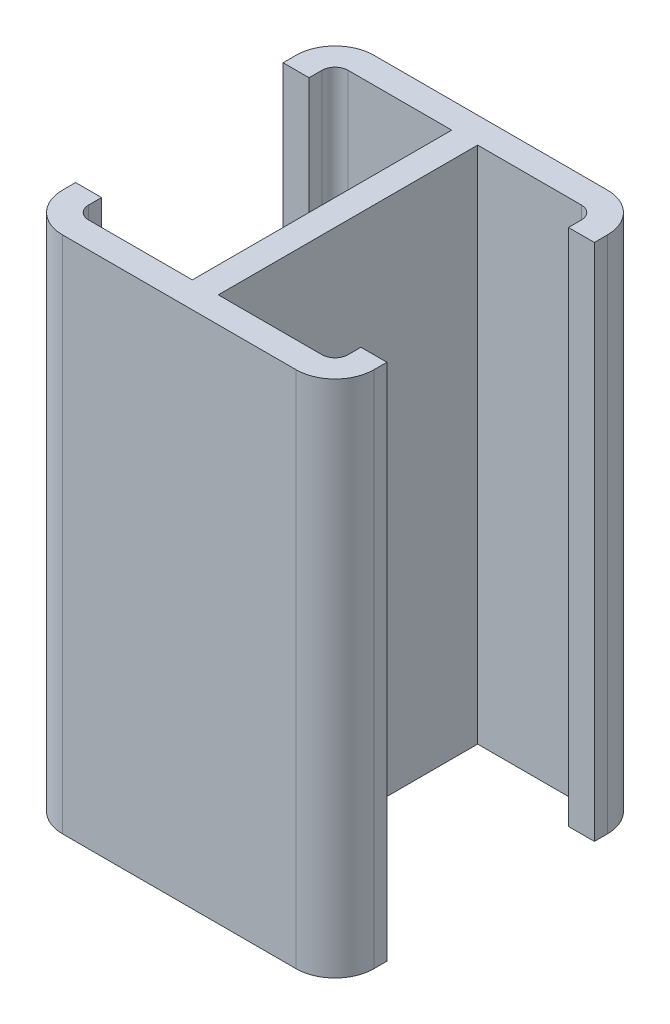
SolidWorks part; units mm, degrees
ref_plane "正面" through (0, 0, 0) normal (0, 0, 1) x (1, 0, 0)
ref_plane "平面" through (0, 0, 0) normal (0, 1, 0) x (1, 0, 0)
ref_plane "右側面" through (0, 0, 0) normal (1, 0, 0) x (0, 0, -1)
sketch "ｽｹｯﾁ1" plane through (0, 0, 0) normal (0, 1, 0) x (1, 0, 0)
  line L0 (0, 0) -> (0, -60)
  line L1 (0, -60) -> (45, -60)
  line L2 (60, -45) -> (60, -40)
  line L3 (60, -40) -> (50, -40)
  line L4 (50, -40) -> (50, -45)
  line L5 (45, -50) -> (5, -50)
  line L6 (5, -50) -> (5, 0)
  line L7 (5, 0) -> (0, 0)
  arc A0 (60, -45) -> (45, -60) centre (45, -45) cw
  arc A1 (50, -45) -> (45, -50) centre (45, -45) cw
  point P11 (60, -60)
  point P14 (50, -50)
  dimension "D7" = 15
  dimension "D8" = 5
  dimension "D1" = 60
  dimension "D2" = 60
  dimension "D3" = 20
  dimension "D4" = 10
  dimension "D5" = 10
  dimension "D6" = 5
extrude "ﾎﾞｽ - 押し出し1" add sketch "ｽｹｯﾁ1" along normal blind 200
mirror "ﾐﾗｰ1" about plane through (0, 200, 0) normal (1, 0, 0) of bodies 101
mirror "ﾐﾗｰ2" about plane through (5, 200, 0) normal (0, 0, 1) of bodies 104
equation "\"C\" = 20.0"
equation "\"D3@ｽｹｯﾁ1\"=\"C\""
equation "\"B\" = 10.0"
equation "\"D4@ｽｹｯﾁ1\"=\"B\""
equation "\"D5@ｽｹｯﾁ1\"=\"B\""
equation "\"A\" = 10.0"
equation "\"D6@ｽｹｯﾁ1\"=\"A\"/2"
equation "\"D8@ｽｹｯﾁ1\"= \"B\"/2"
equation "\"D7@ｽｹｯﾁ1\"= \"B\"/2*3"
